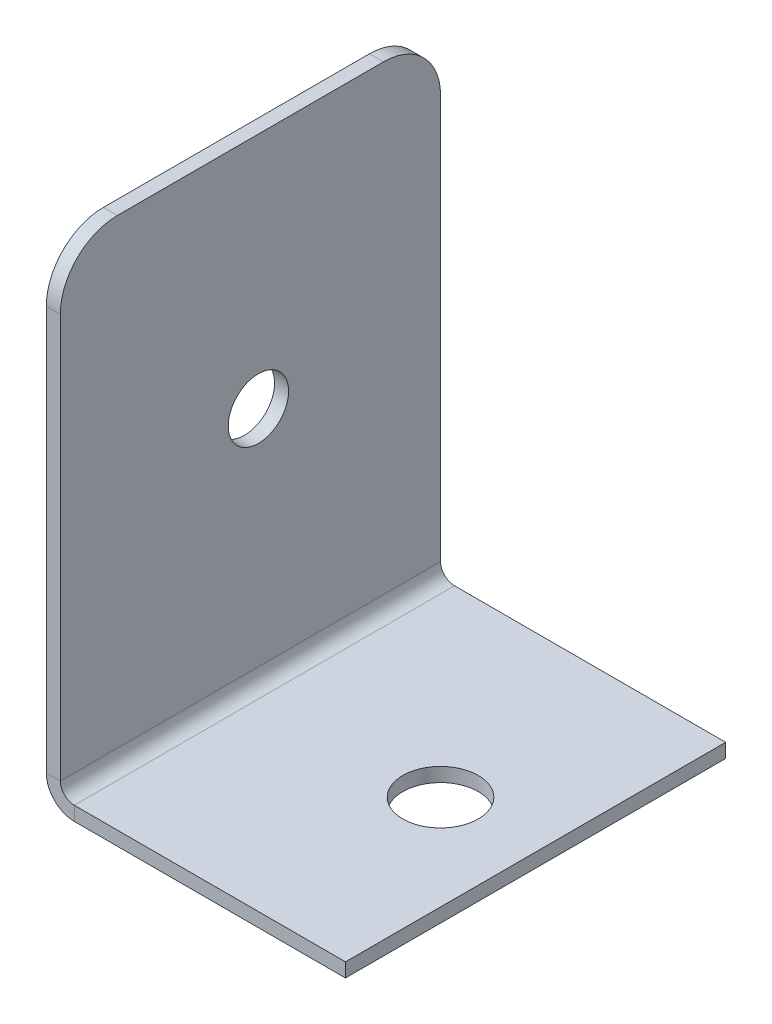
SolidWorks part; units mm, degrees
note: The reader was unsure of these and kept them because the rebuilt part matched: bend radius of "BaseBend1".
material "Plain Carbon Steel"
ref_plane "Front Plane" through (0, 0, 0) normal (0, 0, 1) x (1, 0, 0)
ref_plane "Top Plane" through (0, 0, 0) normal (0, 1, 0) x (1, 0, 0)
ref_plane "Right Plane" through (0, 0, 0) normal (1, 0, 0) x (0, 0, -1)
sketch "Sketch2" plane through (0, 0, 0) normal (0, 0, 1) x (1, 0, 0)
  line L0 (0, 25) -> (0, 0)
  line L1 (0, 0) -> (15, 0)
  dimension "D1" = 15
  dimension "D2" = 25
base flange "Base-Flange1" sketch "Sketch2" end condition mid plane depth 20 reverse direction no thickness 0.7366 reverse thickness direction no bend radius 0.7366
bend "BaseBend1" bend radius 0.7366 bend angle 90 parameters "D5"=1
sketch "Sketch7" plane through (0, 0, 0) normal (1, 0, 0) x (0, 0, -1)
  line L0 (-10, -0.7366) -> (10, -0.7366) construction
  line L1 (-10, 25) -> (-10, 0.7366) construction
  circle A0 centre (0.42, 12.4934) radius 1.5875
  point P4 (-10, 12.8683)
  dimension "D1" = 3.175
  dimension "D2" = 13.23
  dimension "D3" = 10.42
extrude "Cut-Extrude1" cut sketch "Sketch7" against normal through all normal cut yes
sketch "Sketch8" plane through (0, 0, 0) normal (0, 1, 0) x (1, 0, 0)
  line L1 (15, -10) -> (15, 10) construction
  circle A0 centre (10, 0) radius 1.9844
  dimension "D1" = 3.9688
  dimension "D2" = 5
extrude "Cut-Extrude2" cut sketch "Sketch8" against normal through all normal cut yes
fillet "Fillet1" radius 3 2 edges at (-0.3683, 25, -10) (-0.3683, 25, 10)
sketch "Bend-Lines1" [suppressed] plane through (0, 0, 0) normal (0, 1, 0) x (1, 0, 0)
sketch "Bounding-Box1" [suppressed] plane through (0, 0, 0) normal (0, 1, 0) x (1, 0, 0)
sheet metal parameters "Sheet-Metal3" thickness 0.7366 parameters "D1"=0.7366
flat pattern "Flat-Pattern3" [suppressed]
sketch "Bend-Lines2" plane through (0, 0, 0) normal (0, 1, 0) x (1, 0, 0)
sketch "Bounding-Box2" [suppressed] plane through (0, 0, 0) normal (0, 1, 0) x (1, 0, 0)
bend of the flat pattern "Flatten-<BaseBend1>1"
sheet metal parameters "Sheet-Metal4" thickness 0.7366 parameters "D1"=0.7366
flat pattern "Flat-Pattern3" [suppressed]
sketch "Bend-Lines2" plane through (0, 0, 0) normal (0, 1, 0) x (1, 0, 0)
sketch "Bounding-Box2" [suppressed] plane through (0, 0, 0) normal (0, 1, 0) x (1, 0, 0)
bend of the flat pattern "Flatten-<BaseBend1>1"
sheet metal parameters "Sheet-Metal5" thickness 0.7366 parameters "D1"=0.7366
flat pattern "Flat-Pattern3"
sketch "Bend-Lines2" plane through (0, 0, 0) normal (1, 0, 0) x (0, 0, -1)
  line L0 (10, -0.1312) -> (-10, -0.1312) construction
  line L1 (10, -0.1312) -> (-10, -0.1312) construction
sketch3d "Bounding-Box2" [suppressed]
  line L0 (0, -40.2624, 0) -> (0, 0, 0) construction
  line L1 (20, -40.2624, 0) -> (20, 0, 0) construction
  line L2 (0, -40.2624, 0) -> (20, -40.2624, 0) construction
  line L3 (0, 0, 0) -> (20, 0, 0) construction
bend of the flat pattern "Flatten-<BaseBend1>1"
